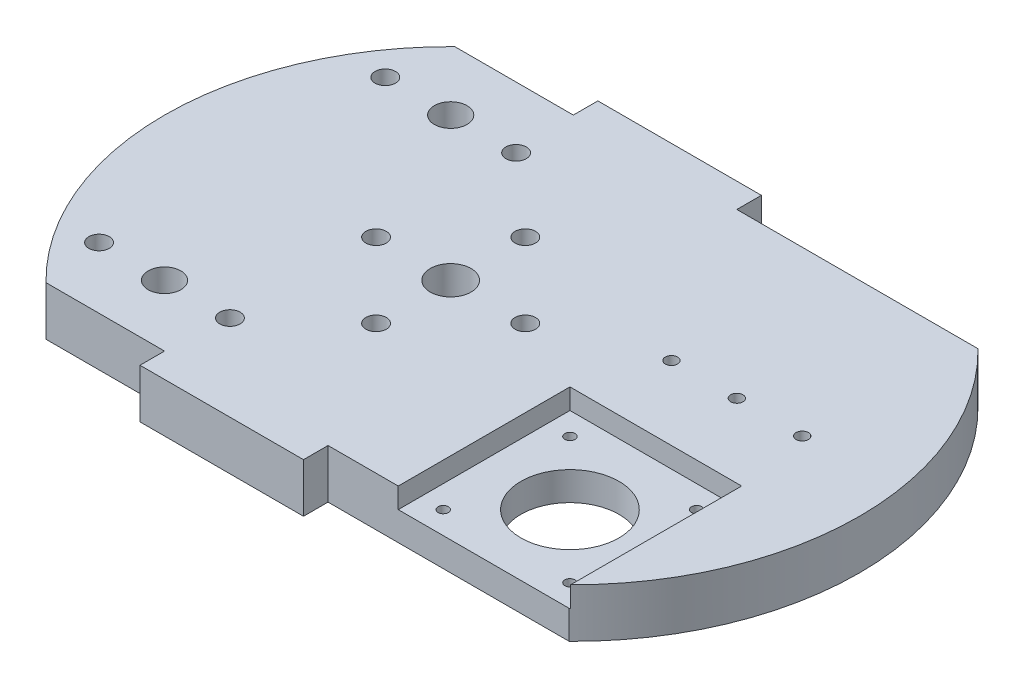
SolidWorks part; units mm, degrees
ref_plane "Front Plane" through (0, 0, 0) normal (0, 0, 1) x (1, 0, 0)
ref_plane "Top Plane" through (0, 0, 0) normal (0, 1, 0) x (1, 0, 0)
ref_plane "Right Plane" through (0, 0, 0) normal (1, 0, 0) x (0, 0, -1)
sketch "Sketch1" plane through (0, 0, 0) normal (0, 1, 0) x (1, 0, 0)
  line L1 (-75, 75) -> (75, 75)
  line L2 (-75, 75) -> (-75, -75)
  line L3 (-75, -75) -> (75, -75)
  line L4 (75, 75) -> (75, -75)
  line L5 (-75, 75) -> (75, -75) construction
  line L6 (-75, -75) -> (75, 75) construction
  point P0 (0, 0)
  dimension "D1" = 150
extrude "Boss-Extrude1" add sketch "Sketch1" along normal blind 12
sketch "Sketch8" plane through (0, 12, 0) normal (0, 1, 0) x (1, 0, 0)
  line L0 (0, 0) -> (-25, 0) construction
  line L1 (-25, 0) -> (-25, -25) construction
  line L2 (0, 0) -> (0, 50) construction
  line L3 (-48.9898, 50) -> (-20, 50)
  line L4 (-48.9898, -50) -> (-20, -50)
  line L16 (20, 56) -> (-20, 56)
  line L17 (-20, 50) -> (-20, 56)
  line L18 (20, -56) -> (-20, -56)
  line L19 (-20, -50) -> (-20, -56)
  line L20 (20, 50) -> (48.9898, 50)
  line L21 (20, -50) -> (48.9898, -50)
  line L22 (20, -50) -> (20, -56)
  line L23 (20, 50) -> (20, 56)
  line L24 (-100, 100) -> (100, 100)
  line L25 (-100, 100) -> (-100, -100)
  line L26 (-100, -100) -> (100, -100)
  line L27 (100, 100) -> (100, -100)
  line L28 (-100, 100) -> (100, -100) construction
  line L29 (-100, -100) -> (100, 100) construction
  arc A2 (-48.9898, 50) -> (-48.9898, -50) centre (0, 0) ccw
  arc A3 (48.9898, -50) -> (48.9898, 50) centre (0, 0) ccw
  dimension "D3" = 200
  dimension "D4" = 140
  dimension "D1" = 25
  dimension "D2" = 25
  dimension "D5" = 50
  dimension "D7" = 20
extrude "Cut-Extrude7" cut sketch "Sketch8" against normal blind 15
sketch "Sketch11" plane through (0, 12, 0) normal (0, 1, 0) x (1, 0, 0)
  line L2 (0, 0) -> (30, 0) construction
  line L3 (48.9898, 50) -> (78.9898, 50)
  line L4 (48.9898, -50) -> (78.9898, -50)
  arc A0 (48.9898, -50) -> (48.9898, 50) centre (0, 0) ccw
  arc A1 (78.9898, -50) -> (78.9898, 50) centre (30, 0) ccw
  dimension "D1" = 140
  dimension "D3" = 30
extrude "Boss-Extrude2" add sketch "Sketch11" against normal up to surface (12 mm away) up to face at (0, 0, 0)
sketch "Sketch6" plane through (0, 12, 0) normal (0, 1, 0) x (1, 0, 0)
  line L0 (0, 0) -> (58.1722, 0) construction
  line L1 (58.1722, 0) -> (58.1722, -29) construction
  line L6 (58.1722, -29) -> (0, 0) construction
  line L8 (37.1722, -8) -> (79.1722, -8)
  line L9 (37.1722, -8) -> (37.1722, -50)
  line L10 (37.1722, -50) -> (79.1722, -50)
  line L11 (79.1722, -8) -> (79.1722, -50)
  line L12 (37.1722, -8) -> (79.1722, -50) construction
  line L13 (37.1722, -50) -> (79.1722, -8) construction
  dimension "D1" = 65
  dimension "D2" = 29
  dimension "D3" = 42
extrude "Cut-Extrude5" cut sketch "Sketch6" against normal blind 5
sketch "Sketch9" plane through (0, 12, 0) normal (0, 1, 0) x (1, 0, 0)
  line L0 (0, 0) -> (-35, 0) construction
  line L1 (-35, 0) -> (-35, 35) construction
  line L2 (-35, 35) -> (-19, 35) construction
  circle A0 centre (-35, 35) radius 4
  circle A1 centre (-35, -35) radius 4
  circle A2 centre (-19, 35) radius 2.5
  circle A3 centre (-51, 35) radius 2.5
  circle A4 centre (-19, -35) radius 2.5
  circle A5 centre (-51, -35) radius 2.5
  dimension "D3" = 8
  dimension "D5" = 5
  dimension "D1" = 35
  dimension "D2" = 35
  dimension "D4" = 16
extrude "Cut-Extrude8" cut sketch "Sketch9" against normal blind 15
sketch "Sketch10" plane through (0, 7, 0) normal (0, 1, 0) x (1, 0, 0)
  line L0 (37.1722, -29) -> (58.1722, -29) construction
  line L1 (37.1722, -8) -> (37.1722, -50) construction
  line L3 (42.6722, -13.5) -> (73.6722, -13.5) construction
  line L4 (42.6722, -13.5) -> (42.6722, -44.5) construction
  line L5 (42.6722, -44.5) -> (73.6722, -44.5) construction
  line L6 (73.6722, -13.5) -> (73.6722, -44.5) construction
  line L7 (42.6722, -13.5) -> (73.6722, -44.5) construction
  line L8 (42.6722, -44.5) -> (73.6722, -13.5) construction
  circle A0 centre (58.1722, -29) radius 12
  circle A1 centre (42.6722, -13.5) radius 1.25
  circle A2 centre (73.6722, -13.5) radius 1.25
  circle A3 centre (42.6722, -44.5) radius 1.25
  circle A4 centre (73.6722, -44.5) radius 1.25
  dimension "D2" = 24
  dimension "D4" = 2.5
  dimension "D5" = 2.5
  dimension "D6" = 2.5
  dimension "D7" = 2.5
  dimension "D1" = 21
  dimension "D3" = 31
extrude "Cut-Extrude9" cut sketch "Sketch10" against normal blind 10
sketch "Sketch12" plane through (0, 12, 0) normal (0, 1, 0) x (1, 0, 0)
  line L0 (0, 0) -> (0, 18.25) construction
  line L1 (0, 0) -> (0, -18.25) construction
  line L2 (0, 0) -> (60, 0) construction
  line L3 (60, 0) -> (60, 10) construction
  line L4 (60, 10) -> (76, 10) construction
  circle A0 centre (0, 18.25) radius 2.5
  circle A1 centre (0, -18.25) radius 2.5
  circle A2 centre (0, 0) radius 5
  circle A3 centre (18.25, 0) radius 2.5
  circle A4 centre (-18.25, 0) radius 2.5
  circle A5 centre (76, 10) radius 1.5
  circle A6 centre (60, 10) radius 1.5
  circle A7 centre (44, 10) radius 1.5
  point P14 (0, 0)
  dimension "D3" = 5
  dimension "D4" = 5
  dimension "D5" = 10
  dimension "D10" = 3
  dimension "D11" = 3
  dimension "D1" = 18.25
  dimension "D2" = 18.25
  dimension "D7" = 60
  dimension "D8" = 10
  dimension "D9" = 16
  dimension "D6" = 2
extrude "Cut-Extrude10" cut sketch "Sketch12" against normal blind 20
sketch "Sketch14" plane through (0, 12, 0) normal (0, 1, 0) x (1, 0, 0)
  arc A0 (79.1722, -49.8207) -> (78.9898, 50) centre (30, 0) ccw construction
  point P0 (99.9999, 0.1279)
sketch "Sketch15" plane through (0, 0, 0) normal (0, -1, 0) x (1, 0, 0)
  arc A0 (78.9898, -50) -> (78.9898, 50) centre (30, 0) ccw construction
  point P0 (100, 0)
ref_axis "Axis1" through (100, 0, 0) along (0, 0.9999, -0.0107)
sketch "Sketch16" plane through (0, 0, 0) normal (0, -1, 0) x (1, 0, 0)
  circle A0 centre (0, 0) radius 26
  dimension "D1" = 52
extrude "Cut-Extrude11" cut sketch "Sketch16" against normal blind 3
sketch "Sketch17" plane through (0, 3, 0) normal (0, -1, 0) x (1, 0, 0)
  circle A0 centre (0, 18.25) radius 5
  circle A1 centre (0, -18.25) radius 5
  dimension "D1" = 10
  dimension "D2" = 10
extrude "Cut-Extrude12" cut sketch "Sketch17" against normal blind 3
